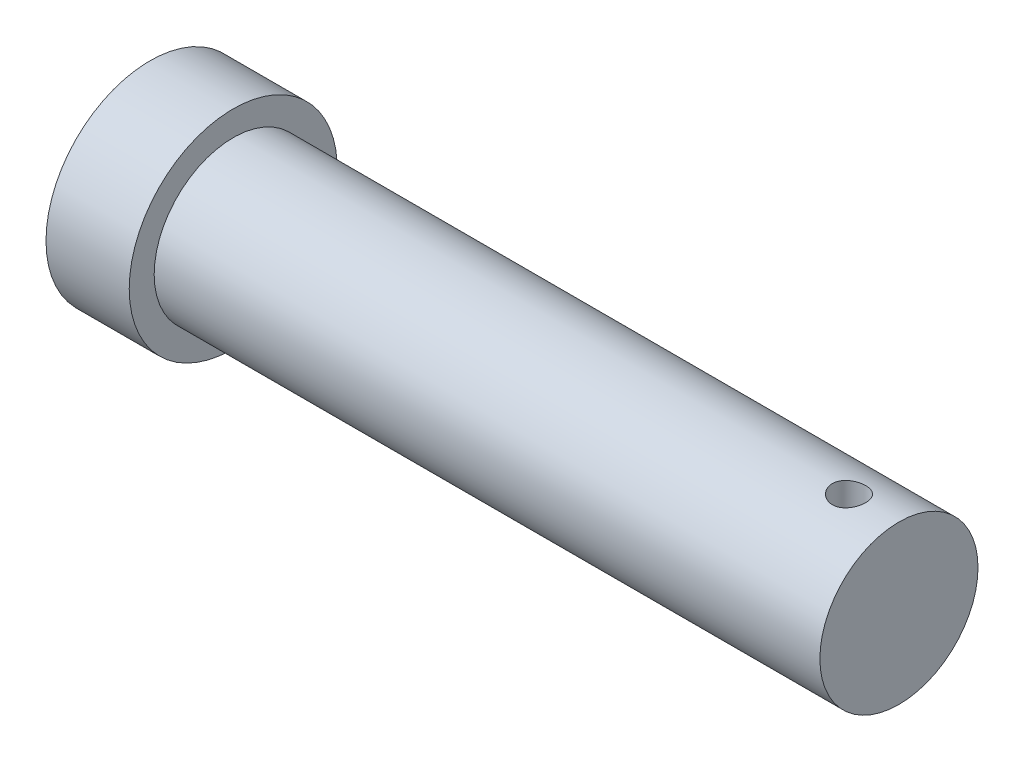
SolidWorks part; units mm, degrees
ref_plane "Front Plane" through (0, 0, 0) normal (0, 0, 1) x (1, 0, 0)
ref_plane "Top Plane" through (0, 0, 0) normal (0, 1, 0) x (1, 0, 0)
ref_plane "Right Plane" through (0, 0, 0) normal (1, 0, 0) x (0, 0, -1)
sketch "Sketch1" plane through (0, 0, 0) normal (1, 0, 0) x (0, 0, -1)
  circle A0 centre (0, 0) radius 1.9
  dimension "D1" = 3.8
extrude "Boss-Extrude1" add sketch "Sketch1" along normal blind 18 contours A0
sketch "Sketch2" plane through (0, 0, 0) normal (0, 1, 0) x (1, 0, 0)
  line L0 (18, 0) -> (16.8, 0) construction
  line L1 (18, -1.9) -> (18, 1.9) construction
  line L2 (-2.2, 0) -> (2.2, 0) construction
  line L3 (0, 0) -> (0.8, 0) construction
  line L4 (0.8, 0) -> (5.8, 0) construction
  line L5 (16.8, 0) -> (11.8, 0) construction
  circle A0 centre (16.8, 0) radius 0.4
  dimension "D1" = 1.2
  dimension "D2" = 5
extrude "Cut-Extrude1" cut sketch "Sketch2" against normal blind 10 and the other way blind 10
sketch "Sketch3" plane through (0, 0, 0) normal (-1, 0, 0) x (0, 0, 1)
  circle A0 centre (0, 0) radius 2.5
extrude "Boss-Extrude2" add sketch "Sketch3" against normal blind 2
scale "Scale1" scale about origin uniform scaling yes scale factor 1.5
